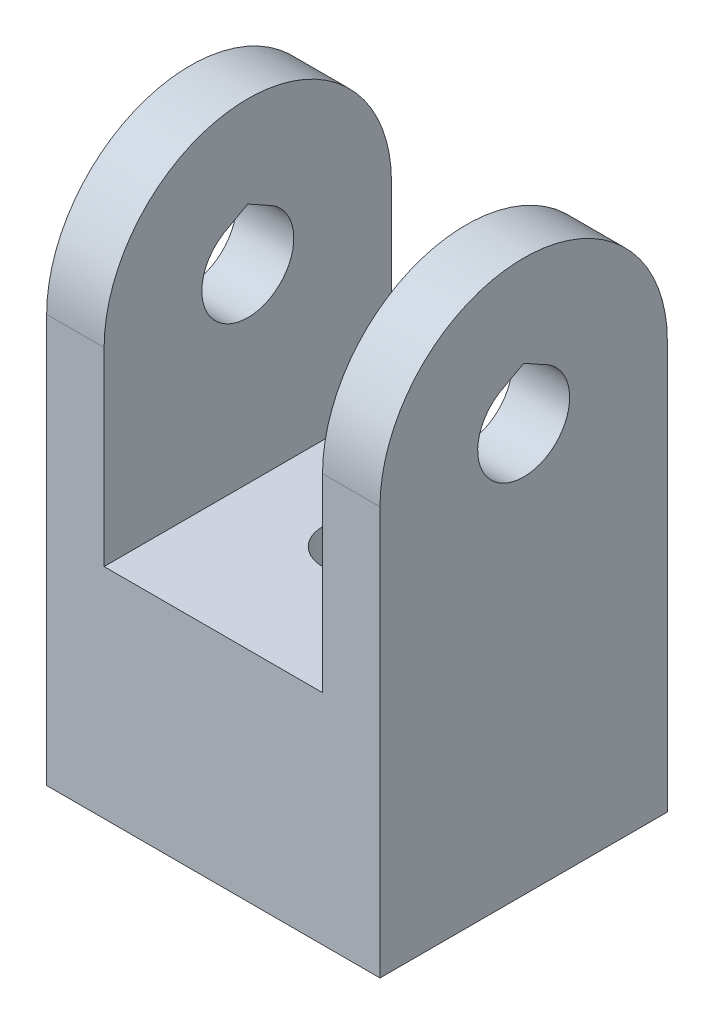
SolidWorks part; units mm, degrees
material "Polybutadiene (PB)"
ref_plane "Front Plane" through (0, 0, 0) normal (0, 0, 1) x (1, 0, 0)
ref_plane "Top Plane" through (0, 0, 0) normal (0, 1, 0) x (1, 0, 0)
ref_plane "Right Plane" through (0, 0, 0) normal (1, 0, 0) x (0, 0, -1)
sketch "Sketch1" plane through (0, 0, 0) normal (0, 0, 1) x (1, 0, 0)
  line L1 (0, 0) -> (29, 0)
  line L2 (0, 0) -> (0, 50)
  line L3 (0, 50) -> (29, 50)
  line L4 (29, 0) -> (29, 50)
  dimension "D1" = 29
  dimension "D2" = 50
extrude "Boss-Extrude1" add sketch "Sketch1" along normal blind 25
sketch "Sketch2" plane through (0, 0, 25) normal (0, 0, 1) x (1, 0, 0)
  line L0 (14.5, 50) -> (14.5, 11.8953) construction
  line L1 (29, 50) -> (0, 50) construction
  line L3 (5, 79) -> (24, 79)
  line L4 (5, 79) -> (5, 21)
  line L5 (5, 21) -> (24, 21)
  line L6 (24, 79) -> (24, 21)
  line L7 (5, 79) -> (24, 21) construction
  line L8 (5, 21) -> (24, 79) construction
  dimension "D1" = 19
  dimension "D2" = 58
extrude "Cut-Extrude1" cut sketch "Sketch2" against normal blind 25
fillet "Fillet2" 2 edges at (26.5, 50, 25) (26.5, 50, 0) type full round first side face at (14.5, 30.25, 25) second side face at (14.5, 30.25, 0) middle face at (26.5, 50, 12.5)
fillet "Fillet3" 2 edges at (2.5, 50, 25) (2.5, 50, 0) type full round first side face at (14.5, 27.125, 25) second side face at (14.5, 27.125, 0) middle face at (2.5, 50, 12.5)
sketch "Sketch3" plane through (0, 0, 0) normal (0, -1, 0) x (1, 0, 0)
  line L0 (29, 12.5) -> (11.8962, 12.5) construction
  line L1 (29, 25) -> (29, 0) construction
  line L2 (11.8962, 12.5) -> (14.5, 0) construction
  line L3 (0, 0) -> (29, 0) construction
  line L4 (14.5, 0) -> (14.5, 13.0424) construction
  circle A0 centre (14.5, 12.5) radius 3
  dimension "D1" = 6
extrude "Cut-Extrude2" cut sketch "Sketch3" against normal blind 25
sketch "Sketch4" plane through (29, 0, 0) normal (1, 0, 0) x (0, 0, -1)
  line L0 (-12.5, 37.5) -> (-12.5, 43.2819) construction
  line L1 (-14.1483, 41.1446) -> (-12.5, 42.0629)
  line L2 (-10.8517, 41.1446) -> (-12.5, 42.0629)
  arc A0 (0, 37.5) -> (-25, 37.5) centre (-12.5, 37.5) ccw construction
  arc A1 (-14.1483, 41.1446) -> (-10.8517, 41.1446) centre (-12.5, 37.5) ccw
  point P0 (-12.5, 37.5)
  point P10 (-14.1483, 41.1446)
  point P11 (-12.5, 42.2169)
  point P12 (-12.5, 42.0629)
  point P13 (0, 0)
  dimension "D1" = 8
extrude "Cut-Extrude3" cut sketch "Sketch4" against normal blind 45
sketch "Sketch5" plane through (0, 0, 0) normal (0, 0, -1) x (-1, 0, 0)
  line L0 (-14.5, 21) -> (-14.5, 0) construction
  line L1 (-5, 21) -> (-24, 21) construction
  line L2 (-14.5, 0) -> (0, 10.5) construction
  line L3 (0, 37.5) -> (0, 0) construction
  line L4 (0, 10.5) -> (-29, 10.5) construction
  line L5 (0, 0) -> (-29, 0) construction
  line L6 (-24, 5) -> (-5, 5)
  line L7 (-24, 5) -> (-24, 16)
  line L8 (-24, 16) -> (-5, 16)
  line L9 (-5, 5) -> (-5, 16)
  line L10 (-24, 5) -> (-5, 16) construction
  line L11 (-24, 16) -> (-5, 5) construction
  line L12 (-29, 0) -> (-29, 37.5) construction
  point P8 (-14.5, 10.5)
  dimension "D1" = 5
  dimension "D2" = 5
  dimension "D3" = 5
extrude "Cut-Extrude4" cut sketch "Sketch5" against normal offset from surface (20 mm away) 5 up to face at (14.5, 24, 25)
chamfer "Chamfer1" distance 2 angle 45 4 edges at (29, 0, 12.5) (14.5, 0, 25) (0, 0, 12.5) (14.5, 0, 0)
